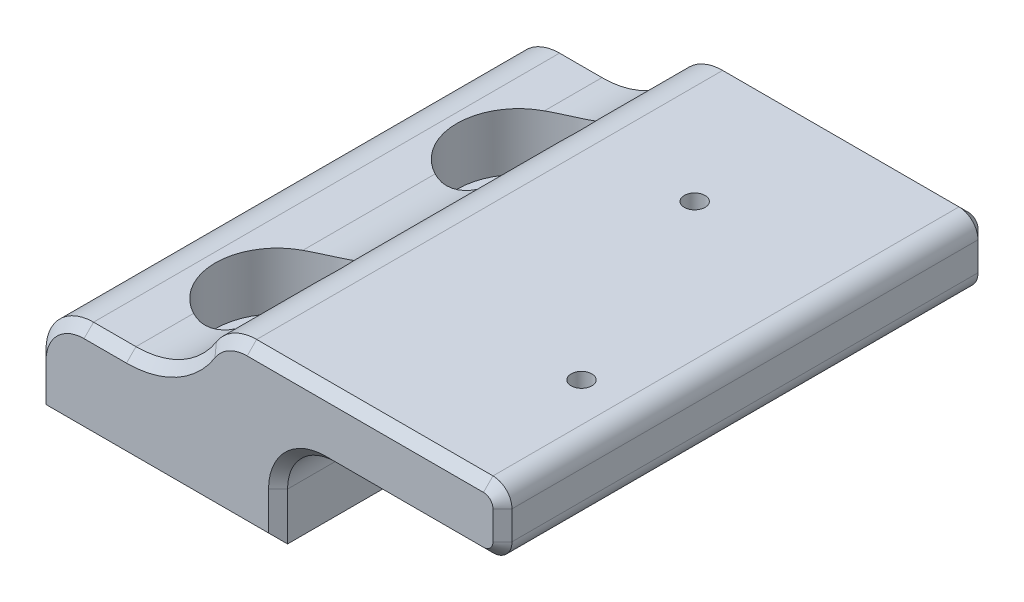
SolidWorks part; units mm, degrees
note: The reader was unsure of these and kept them because the rebuilt part matched: shared geometry of "Sketch3<4>".
ref_plane "Front Plane" through (0, 0, 0) normal (0, 0, 1) x (1, 0, 0)
ref_plane "Top Plane" through (0, 0, 0) normal (0, 1, 0) x (1, 0, 0)
ref_plane "Right Plane" through (0, 0, 0) normal (1, 0, 0) x (0, 0, -1)
sketch "Sketch1" plane through (0, 0, 0) normal (0, 0, 1) x (1, 0, 0)
  line L0 (-22.2, -8.5) -> (3.2, -8.5)
  line L5 (3.2, -8.5) -> (3.2, 1.5)
  line L6 (3.2, 1.5) -> (26.8, 1.5)
  line L7 (26.8, 1.5) -> (26.8, 8.5)
  line L8 (26.8, 8.5) -> (-3.2, 8.5)
  line L9 (-3.2, 8.5) -> (-3.2, 1.5)
  line L10 (-3.2, 1.5) -> (-22.2, 1.5)
  line L11 (-22.2, 1.5) -> (-22.2, -8.5)
  line L12 (0, 8.5) -> (0, -8.5) construction
  line L13 (-3.2, 0) -> (3.2, 0) construction
  point P13 (0, 0)
  point P22 (0, 0)
  dimension "D1" = 10
  dimension "D2" = 30
  dimension "D3" = 25.4
  dimension "D4" = 19
  dimension "D5" = 10
  dimension "D6" = 7
extrude "Boss-Extrude1" add sketch "Sketch1" along normal mid plane 51
sketch "Sketch3" plane through (0, 1.5, 0) normal (0, 1, 0) x (1, 0, 0)
  line L0 (-3.2, -25.5) -> (-3.2, 25.5) construction
  circle A0 centre (-9.7, -12.7) radius 6.5
  circle A1 centre (-9.7, -12.7) radius 4
  dimension "D1" = 13
  dimension "D2" = 8
  dimension "D3" = 12.7
extrude "Cut-Extrude1" cut sketch "Sketch3" against normal through all contours A1
extrude "Cut-Extrude2" cut sketch "Sketch3<4>" against normal blind 6
sketch "Sketch3<4>" plane through (0, 1.5, 0) normal (0, 1, 0) x (1, 0, 0) same geometry as "Sketch3"
mirror "Mirror1" about plane through (0, 0, 0) normal (0, 0, 1) of "Cut-Extrude2", "Cut-Extrude1"
sketch "Sketch9" plane through (0, 8.5, 0) normal (0, 1, 0) x (1, 0, 0)
  line L0 (10.4078, 11.1) -> (20.7078, -11.1) construction
  line L1 (26.8, -25.5) -> (26.8, 25.5) construction
  circle A0 centre (10.4078, 11.1) radius 1.0922
  circle A1 centre (20.7078, -11.1) radius 1.0922
  point P4 (15.5578, 0)
  dimension "D3" = 2.1844
  dimension "D1" = 22.2
  dimension "D2" = 10.3
  dimension "D4" = 5
extrude "Cut-Extrude3" cut sketch "Sketch9" against normal through all
fillet "Fillet1" radius 10 3 edges at (-3.2, 1.5, 19.1) (-3.2, 1.5, -19.1) (-3.2, 1.5, 0)
fillet "Fillet2" radius 5 3 edges at (-3.2, 8.5, -19.1) (3.2, 1.5, 0) (-22.2, 1.5, 0)
fillet "Fillet4" radius 2 2 edges at (26.8, 8.5, 0) (26.8, 1.5, 0)
chamfer "Chamfer1" distance 1 angle 45 26 edges at (26.8, 5, 25.5) (16.5, 1.5, 25.5) (4.6645, 0.0355, 25.5) (3.2, -6, 25.5) (-9.5, -8.5, 25.5) (-22.2, -6, 25.5) (-14.9697, 1.5, 25.5) (-7.9089, 2.744, 25.5) (-2.466, 7.878, 25.5) (12.3746, 8.5, 25.5) (-14.9697, 1.5, -25.5) (-22.2, -6, -25.5) (-9.5, -8.5, -25.5) (3.2, -6, -25.5) (4.6645, 0.0355, -25.5) (16.5, 1.5, -25.5) (26.8, 5, -25.5) (12.3746, 8.5, -25.5) (-2.466, 7.878, -25.5) (-7.9089, 2.744, -25.5) (26.2142, 2.0858, 25.5) (-20.7355, 0.0355, 25.5) (26.2142, 7.9142, 25.5) (-20.7355, 0.0355, -25.5) (26.2142, 2.0858, -25.5) (26.2142, 7.9142, -25.5)
